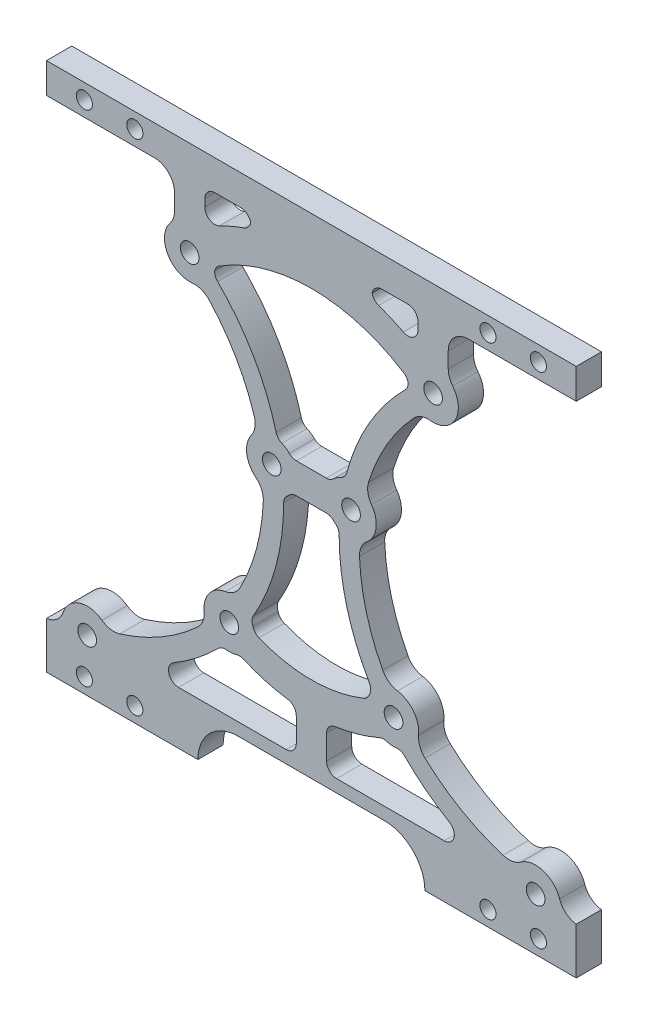
SolidWorks part; units mm, degrees
ref_plane "前视基准面" through (0, 0, 0) normal (0, 0, 1) x (1, 0, 0)
ref_plane "上视基准面" through (0, 0, 0) normal (0, 1, 0) x (1, 0, 0)
ref_plane "右视基准面" through (0, 0, 0) normal (1, 0, 0) x (0, 0, -1)
sketch "草图1" plane through (0, 0, 0) normal (0, 0, 1) x (1, 0, 0)
  line L1 (-50, 0) -> (-50, -42.5) construction
  line L2 (-55, 49.7494) -> (-55, 55)
  line L7 (-55, -49.7494) -> (-55, -55)
  line L8 (55, -55) -> (-55, -55)
  line L9 (-55, 55) -> (55, 55)
  line L10 (0, -55) -> (0, 55) construction
  line L11 (50, 0) -> (50, -42.5) construction
  line L12 (55, -49.7494) -> (55, -55)
  line L13 (55, 49.7494) -> (55, 55)
  arc A1 (-50, -42.5) -> (-44.4526, -42.1364) centre (-50, 0) ccw construction
  circle A2 centre (-44.4526, -42.1364) radius 1.85
  circle A3 centre (-75.8724, -33.7175) radius 1.85
  circle A4 centre (-92.1364, -5.5474) radius 1.85
  circle A5 centre (-83.7175, 25.8724) radius 1.85
  circle A6 centre (-55.5474, 42.1364) radius 1.85
  circle A7 centre (-24.1276, 33.7175) radius 1.85
  circle A8 centre (-7.8636, 5.5474) radius 1.85
  circle A9 centre (-16.2825, -25.8724) radius 1.85
  circle A10 centre (-50, 0) radius 37
  arc A11 (-55, 49.7494) -> (-55, -49.7494) centre (-50, 0) ccw
  arc A12 (50, -42.5) -> (44.4526, -42.1364) centre (50, 0) cw construction
  arc A13 (55, 49.7494) -> (55, -49.7494) centre (50, 0) cw
  circle A14 centre (50, 0) radius 37
  circle A15 centre (16.2825, -25.8724) radius 1.85
  circle A16 centre (7.8636, 5.5474) radius 1.85
  circle A17 centre (24.1276, 33.7175) radius 1.85
  circle A18 centre (55.5474, 42.1364) radius 1.85
  circle A19 centre (83.7175, 25.8724) radius 1.85
  circle A20 centre (92.1364, -5.5474) radius 1.85
  circle A21 centre (75.8724, -33.7175) radius 1.85
  circle A22 centre (44.4526, -42.1364) radius 1.85
  circle A25 centre (8, -47.5) radius 2.1
  circle A27 centre (-8, -47.5) radius 2.1
  point P23 (-50, 0)
  point P26 (50, 0)
  point P50 (0, 55)
  point P51 (0, -55)
  dimension "D1" = 8
extrude "凸台-拉伸1" add sketch "草图1" along normal blind 5
fillet "圆角1" radius 2.5 8 edges at (-55, -49.7494, 2.5) (-55, -55, 2.5) (55, -55, 2.5) (55, -49.7494, 2.5) (55, 49.7494, 2.5) (55, 55, 2.5) (-55, 55, 2.5) (-55, 49.7494, 2.5)
sketch "草图2" plane through (0, 0, 5) normal (0, 0, 1) x (1, 0, 0)
  line L0 (-52.5, 55) -> (-52.5, 52.5)
  line L1 (-52.5, 52.5) -> (52.5, 52.5)
  line L2 (55, 0) -> (-55, 0) construction
  line L3 (-52.5, -52.5) -> (52.5, -52.5)
  line L4 (-52.5, -55) -> (-52.5, -52.5)
  line L5 (0, -55) -> (0, 55) construction
  line L6 (52.5, -55) -> (52.5, -52.5)
  line L7 (52.5, 55) -> (52.5, 52.5)
  line L8 (-52.5, 55) -> (52.5, 55)
  line L9 (52.5, -55) -> (-52.5, -55)
  point P13 (0, -52.5)
  point P14 (0, 52.5)
extrude "切除-拉伸1" cut sketch "草图2" against normal blind 10
sketch "草图3" plane through (0, 0, 5) normal (0, 0, 1) x (1, 0, 0)
  line L0 (-52.5, 52.5) -> (-52.5, -52.5)
  line L1 (-52.5, -52.5) -> (52.5, -52.5)
  line L2 (52.5, -52.5) -> (52.5, 52.5)
  line L3 (52.5, 52.5) -> (-52.5, 52.5)
extrude "切除-拉伸2" cut sketch "草图3" against normal blind 10 flip side to cut
sketch "草图5" plane through (0, 0, 5) normal (0, 0, 1) x (1, 0, 0)
  line L0 (0, -2.75) -> (0, 2.75) construction
  line L2 (2.75, 0) -> (-2.75, 0) construction
  circle A2 centre (-45, 49.5) radius 1.6
  circle A5 centre (-35, 49.5) radius 1.6
  circle A6 centre (35, 49.5) radius 1.6
  circle A7 centre (45, 49.5) radius 1.6
  circle A8 centre (45, -49.5) radius 1.6
  circle A9 centre (35, -49.5) radius 1.6
  circle A10 centre (-35, -49.5) radius 1.6
  circle A11 centre (-45, -49.5) radius 1.6
extrude "切除-拉伸3" cut sketch "草图5" against normal blind 10
sketch "草图6" plane through (0, 0, 5) normal (0, 0, 1) x (1, 0, 0)
  line L2 (-52.5, 52.5) -> (-52.5, 36.9154) construction
  line L4 (-3.8636, 2.5474) -> (3.8636, 2.5474)
  line L5 (-3.8636, 8.5474) -> (3.8636, 8.5474)
  line L8 (0, -2.75) -> (0, 2.75) construction
  line L9 (-52.5, 46.5) -> (-52.5, 52.5)
  line L13 (-52.5, 52.5) -> (52.5, 52.5) construction
  line L16 (-52.5, 52.5) -> (52.5, 52.5)
  line L19 (-27.1276, 46.5) -> (-52.5, 46.5)
  line L20 (21.1276, 46.5) -> (21.1276, 39.6188)
  line L21 (-27.1276, 37.7175) -> (-27.1276, 46.5)
  line L22 (-21.1276, 46.5) -> (-21.1276, 39.6188)
  line L23 (27.1276, 37.7175) -> (27.1276, 46.5)
  line L24 (52.5, 46.5) -> (27.1276, 46.5)
  line L25 (52.5, 46.5) -> (52.5, 52.5)
  line L26 (-12, 46.5) -> (-21.1276, 46.5)
  line L27 (-12, 46.5) -> (-12, 43.7997)
  line L28 (12, 46.5) -> (12, 43.7997)
  line L29 (12, 46.5) -> (21.1276, 46.5)
  line L31 (-52.5, -43.2631) -> (-52.5, -52.5)
  line L32 (52.5, -52.5) -> (52.5, -36.9154) construction
  line L33 (49.3363, -43.2089) -> (52.5, -43.2631)
  line L34 (52.5, -43.2631) -> (52.5, -52.5)
  line L35 (52.5, -52.5) -> (-52.5, -52.5)
  line L36 (52.5, -52.5) -> (-52.5, -52.5) construction
  line L37 (-49.3363, -43.2089) -> (-52.5, -43.2631)
  line L39 (3, -42.0254) -> (3, -33.4352)
  line L40 (-3, -42.0254) -> (-3, -33.4352)
  line L47 (-3, -42.0254) -> (-35.3674, -42.0254)
  line L48 (3, -42.0254) -> (35.3674, -42.0254)
  arc A1 (-5.5144, 1.1336) -> (-3.8636, 2.5474) centre (-7.8636, 5.5474) ccw
  arc A3 (-15.3461, -20.9608) -> (-20.7843, -28.048) centre (-16.2825, -25.8724) ccw
  arc A5 (-40.3175, -39.3256) -> (-20.7843, -28.048) centre (-50, 0) ccw
  arc A6 (-35.3674, -42.0254) -> (-17.7424, -30.6545) centre (-50, 0) ccw
  arc A8 (-10.6744, 9.6825) -> (-9.5084, 0.8257) centre (-7.8636, 5.5474) ccw
  arc A9 (-10.6744, 9.6825) -> (-21.952, 29.2157) centre (-50, 0) ccw
  arc A10 (-6.7369, 10.4188) -> (-19.3455, 32.2576) centre (-50, 0) ccw
  arc A11 (-15.3461, -20.9608) -> (-9.5084, 0.8257) centre (-50, 0) ccw
  arc A12 (-12.0412, -23.2245) -> (-5.5144, 1.1336) centre (-50, 0) ccw
  arc A13 (-17.7424, -30.6545) -> (-14.2003, -30.4182) centre (-16.2825, -25.8724) ccw
  arc A14 (-3.8636, 8.5474) -> (-6.7369, 10.4188) centre (-7.8636, 5.5474) ccw
  arc A16 (19.1279, 33.7658) -> (-19.1279, 33.7658) centre (0, 5.5474) ccw
  arc A17 (-12, 43.7997) -> (-21.1276, 39.6188) centre (0, 5.5474) ccw
  arc A20 (3.8636, 8.5474) -> (6.7369, 10.4188) centre (7.8636, 5.5474) cw
  arc A21 (17.7424, -30.6545) -> (14.2003, -30.4182) centre (16.2825, -25.8724) cw
  arc A22 (12.0412, -23.2245) -> (5.5144, 1.1336) centre (50, 0) cw
  arc A23 (15.3461, -20.9608) -> (9.5084, 0.8257) centre (50, 0) cw
  arc A24 (6.7369, 10.4188) -> (19.3455, 32.2576) centre (50, 0) cw
  arc A25 (10.6744, 9.6825) -> (21.952, 29.2157) centre (50, 0) cw
  arc A26 (10.6744, 9.6825) -> (9.5084, 0.8257) centre (7.8636, 5.5474) cw
  arc A28 (35.3674, -42.0254) -> (17.7424, -30.6545) centre (50, 0) cw
  arc A29 (40.3175, -39.3256) -> (20.7843, -28.048) centre (50, 0) cw
  arc A30 (15.3461, -20.9608) -> (20.7843, -28.048) centre (16.2825, -25.8724) cw
  arc A31 (40.3175, -39.3256) -> (49.3363, -43.2089) centre (44.4526, -42.1364) cw
  arc A32 (5.5144, 1.1336) -> (3.8636, 2.5474) centre (7.8636, 5.5474) cw
  arc A34 (-19.3455, 32.2576) -> (-19.1279, 33.7658) centre (-24.1276, 33.7175) ccw
  arc A35 (-27.1276, 37.7175) -> (-21.952, 29.2157) centre (-24.1276, 33.7175) ccw
  arc A36 (27.1276, 37.7175) -> (21.952, 29.2157) centre (24.1276, 33.7175) cw
  arc A37 (19.3455, 32.2576) -> (19.1279, 33.7658) centre (24.1276, 33.7175) cw
  arc A38 (12, 43.7997) -> (21.1276, 39.6188) centre (0, 5.5474) cw
  arc A39 (-40.3175, -39.3256) -> (-49.3363, -43.2089) centre (-44.4526, -42.1364) ccw
  arc A40 (3, -33.4352) -> (14.2003, -30.4182) centre (0, 0) ccw
  arc A42 (-14.2003, -30.4182) -> (-3, -33.4352) centre (0, 0) ccw
  arc A43 (-11.3378, -25.1303) -> (11.3378, -25.1303) centre (0, 0) ccw
  arc A44 (-11.3378, -25.1303) -> (-12.0412, -23.2245) centre (-16.2825, -25.8724) ccw
  arc A48 (11.3378, -25.1303) -> (12.0412, -23.2245) centre (16.2825, -25.8724) cw
  point P15 (0, 0)
  point P23 (-7.8636, 2.5474)
  point P26 (7.8636, 2.5474)
  point P27 (-7.8636, 8.5474)
  point P33 (7.8636, 8.5474)
  point P39 (-24.9781, 40.0639)
  point P41 (0, 2.5474)
  point P46 (-35.8957, 50.5)
  point P50 (-21.1276, 33.7175)
  point P70 (-38.6395, -43.0254)
  point P76 (0, 52.5)
  point P77 (0, 46.5)
  point P78 (0, 8.5474)
  point P80 (-27.1276, 33.7175)
  point P81 (0, -52.5)
  point P97 (0, -43.0254)
  point P100 (14.6876, -26.8099)
  point P103 (0, -43.0254)
  point P105 (-17.8804, -28.4114)
  point P106 (16.129, -29.441)
  point P108 (-14.6846, -23.3333)
  point P109 (13.2462, -24.1789)
  point P113 (0, -31.1409)
  point P115 (3, -43.0254)
  point P116 (3, -31.1409)
  point P117 (-3, -43.0254)
  point P118 (-3, -31.1409)
extrude "切除-拉伸4" cut sketch "草图6" against normal blind 10 flip side to cut
fillet "圆角2" radius 4 18 edges at (27.1276, 46.5, 2.5) (27.1276, 37.7175, 2.5) (21.952, 29.2157, 2.5) (10.6744, 9.6825, 2.5) (9.5084, 0.8257, 2.5) (15.3461, -20.9608, 2.5) (20.7843, -28.048, 2.5) (40.3175, -39.3256, 2.5) (49.3363, -43.2089, 2.5) (-27.1276, 46.5, 2.5) (-27.1276, 37.7175, 2.5) (-21.952, 29.2157, 2.5) (-9.5084, 0.8257, 2.5) (-10.6744, 9.6825, 2.5) (-49.3363, -43.2089, 2.5) (-40.3175, -39.3256, 2.5) (-20.7843, -28.048, 2.5) (-15.3461, -20.9608, 2.5)
fillet "圆角3" radius 2 34 edges at (21.1276, 46.5, 2.5) (12, 46.5, 2.5) (12, 43.7997, 2.5) (21.1276, 39.6188, 2.5) (19.3455, 32.2576, 2.5) (19.1279, 33.7658, 2.5) (6.7369, 10.4188, 2.5) (3.8636, 8.5474, 2.5) (3.8636, 2.5474, 2.5) (5.5144, 1.1336, 2.5) (11.3378, -25.1303, 2.5) (12.0412, -23.2245, 2.5) (17.7424, -30.6545, 2.5) (14.2003, -30.4182, 2.5) (3, -33.4352, 2.5) (3, -42.0254, 2.5) (35.3674, -42.0254, 2.5) (-35.3674, -42.0254, 2.5) (-3, -42.0254, 2.5) (-3, -33.4352, 2.5) (-14.2003, -30.4182, 2.5) (-17.7424, -30.6545, 2.5) (-11.3378, -25.1303, 2.5) (-12.0412, -23.2245, 2.5) (-5.5144, 1.1336, 2.5) (-3.8636, 2.5474, 2.5) (-19.3455, 32.2576, 2.5) (-19.1279, 33.7658, 2.5) (-3.8636, 8.5474, 2.5) (-6.7369, 10.4188, 2.5) (-21.1276, 46.5, 2.5) (-21.1276, 39.6188, 2.5) (-12, 46.5, 2.5) (-12, 43.7997, 2.5)
sketch "草图7" plane through (0, 0, 5) normal (0, 0, 1) x (1, 0, 0)
  line L0 (-52.5, -52.5) -> (-22.5, -52.5)
  line L1 (52.5, -52.5) -> (-52.5, -52.5) construction
  line L2 (-14.5, -44.5) -> (14.5, -44.5)
  line L3 (-22.5, -52.5) -> (22.5, -52.5)
  line L4 (0, -2.75) -> (0, 2.75) construction
  line L5 (52.5, -52.5) -> (22.5, -52.5)
  arc A0 (22.5, -52.5) -> (14.5, -44.5) centre (14.5, -52.5) ccw
  arc A1 (-22.5, -52.5) -> (-14.5, -44.5) centre (-14.5, -52.5) cw
  point P6 (0, -44.5)
  point P14 (0, -52.5)
extrude "切除-拉伸5" cut sketch "草图7" against normal blind 10 contours A1 L3 A0 L2 region at (0, -48.6828, 5)
